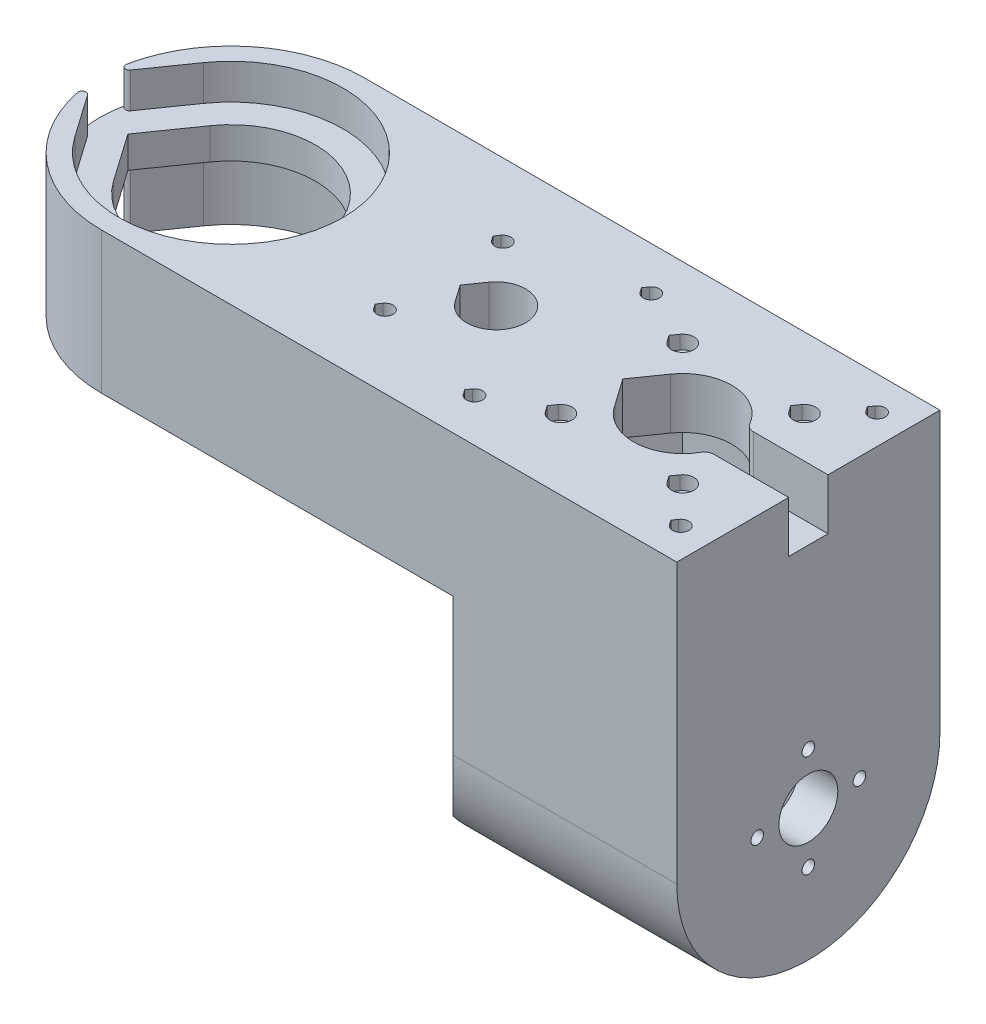
SolidWorks part; units mm, degrees
note: The reader was unsure of these and kept them because the rebuilt part matched: shared geometry of "Sketch2<4>", "Sketch2<5>", "Sketch2<6>", "Sketch3<3>", "Sketch4<3>", "Sketch6<8>", "Sketch6<9>", "Sketch6<10>", "Sketch6<13>", "Sketch6<14>", "Sketch11<3>", "Sketch16<2>".
ref_plane "Front Plane" through (0, 0, 0) normal (1, 0, 0) x (0, 1, 0)
ref_plane "Top Plane" through (0, 0, 0) normal (0, 0, 1) x (0, 1, 0)
ref_plane "Right Plane" through (0, 0, 0) normal (0, 1, 0) x (-1, 0, 0)
sketch "Sketch1" plane through (0, 0, 0) normal (0, 0, 1) x (0, 1, 0)
  line L0 (45, 28.55) -> (54, 28.55)
  line L1 (-7, -93) -> (58, -93)
  line L2 (-7, -93) -> (-7, -137)
  line L3 (-7, -137) -> (58, -137)
  line L4 (58, -93) -> (58, -137)
  line L5 (59, 28.55) -> (68, 28.55)
  line L6 (59, 28.55) -> (59, -28.55)
  line L7 (59, -28.55) -> (68, -28.55)
  line L8 (68, 28.55) -> (68, -28.55)
  line L9 (45, 28.55) -> (45, -28.55)
  line L10 (45, -28.55) -> (54, -28.55)
  line L11 (54, 28.55) -> (54, -28.55)
  line L12 (-13, -147) -> (13, -147)
  line L13 (-30, 30.9464) -> (30, 30.9464) construction
  line L14 (-30, 30.9464) -> (-30, -30.2553) construction
  line L15 (-30, -30.2553) -> (30, -30.2553) construction
  line L16 (30, 30.9464) -> (30, -30.2553) construction
  line L17 (-25, -83) -> (81, -83)
  line L20 (81, -83) -> (81, -147)
  line L21 (81, -83) -> (35, -83)
  line L23 (81, 33.5) -> (35, 33.5)
  line L25 (-25, -147) -> (-13, -147)
  line L26 (-25, -147) -> (-25, -150)
  line L27 (-25, -150) -> (25, -150)
  line L28 (25, -147) -> (25, -150)
  line L29 (13, -147) -> (25, -147)
  line L30 (25, -147) -> (81, -147)
  line L31 (81, -83) -> (81, 33.5)
  line L32 (35, 33.5) -> (35, -83)
  line L33 (-25, -147) -> (-33.5, -147)
  line L34 (-25, -83) -> (-33.5, -83)
  line L35 (-33.5, -83) -> (-33.5, -147)
  point P8 (0, -30.2553)
  point P14 (68, 0)
  point P15 (58, -115)
  point P24 (45, 0)
  point P35 (0, -147)
  dimension "D1" = 65
  dimension "D2" = 44
  dimension "D3" = 57.1
  dimension "D4" = 9
  dimension "D5" = 57.1
  dimension "D6" = 9
  dimension "D7" = 115
  dimension "D8" = 60
  dimension "D9" = 5
  dimension "D10" = 15
  dimension "D11" = 10
  dimension "D12" = 3
  dimension "D13" = 50
  dimension "D14" = 26
  dimension "D15" = 10
  dimension "D16" = 23
  dimension "D17" = 4.95
  dimension "D18" = 10
  dimension "D19" = 10
  dimension "D20" = 8.5
extrude "Boss-Extrude1" add sketch "Sketch1" along normal blind 67
sketch "Sketch2" plane through (0, 81, 0) normal (0, 1, 0) x (-1, 0, 0)
  line L0 (-56.7259, 33.5) -> (49943.2741, 33.5) construction
  line L1 (-147, 67) -> (-147, 0) construction
  line L2 (17.6118, 21.1681) -> (26.2467, 33.5)
  line L3 (-115, -14.8158) -> (-54, -14.8158) construction
  line L4 (-93, 0) -> (-137, 0) construction
  line L5 (-93, 0) -> (-137, 0) construction
  line L9 (-147, 16) -> (-147, 51)
  line L10 (33.5473, 15.9815) -> (-147, 51) construction
  line L11 (33.5482, 51) -> (-147, 16) construction
  line L12 (-54, 18.5) -> (-54, 48.5) construction
  line L13 (-104.0826, 51) -> (-125.9174, 51)
  line L14 (-130.5, 49) -> (-99.5, 49) construction
  line L15 (-130.5, 49) -> (-130.5, 18) construction
  line L16 (-130.5, 18) -> (-99.5, 18) construction
  line L17 (-99.5, 49) -> (-99.5, 18) construction
  line L18 (-130.5, 49) -> (-99.5, 18) construction
  line L19 (-130.5, 18) -> (-99.5, 49) construction
  line L20 (-135.0826, 51) -> (-147, 51)
  line L21 (-135.0826, 16) -> (-147, 16)
  line L22 (-104.0826, 16) -> (-125.9174, 16)
  line L27 (33.5, 67) -> (-21.8575, 67)
  line L28 (33.5, 0) -> (33.5, 67)
  line L29 (33.5, 67) -> (-147, 67) construction
  line L30 (33.5, 0) -> (-21.8575, 0)
  line L31 (28.55, 0) -> (-28.55, 0) construction
  line L34 (23.3868, 17.1244) -> (34.8531, 33.5)
  line L35 (34.8531, 33.5) -> (23.3868, 49.8756)
  line L36 (26.2467, 33.5) -> (17.6118, 45.8319)
  line L37 (-94.9174, 16) -> (-66.0711, 16)
  line L38 (-94.9174, 51) -> (-66.0711, 51)
  line L39 (-61.0711, 11) -> (-61.0711, 0)
  line L40 (33.5, 0) -> (-147, 0) construction
  line L41 (-61.0711, 56) -> (-61.0711, 67)
  line L42 (33.5, 67) -> (-147, 67) construction
  line L43 (-61.0711, 0) -> (-21.8575, 0)
  line L44 (-61.0711, 67) -> (-21.8575, 67)
  arc A0 (23.3868, 49.8756) -> (23.3868, 17.1244) centre (0, 33.5) ccw
  arc A2 (-39.8663, 36.7683) -> (-39.8653, 30.2204) centre (0, 33.5) ccw
  arc A5 (-135.0826, 16) -> (-125.9174, 16) centre (-130.5, 18) ccw
  arc A6 (-104.0826, 16) -> (-94.9174, 16) centre (-99.5, 18) ccw
  arc A9 (-125.9174, 51) -> (-135.0826, 51) centre (-130.5, 49) ccw
  arc A11 (-94.9174, 51) -> (-104.0826, 51) centre (-99.5, 49) ccw
  arc A12 (17.6118, 45.8319) -> (17.6118, 21.1681) centre (0, 33.5) ccw
  arc A13 (17.6118, 45.8319) -> (17.6118, 21.1681) centre (0, 33.5) cw construction
  arc A15 (23.3868, 17.1244) -> (23.3868, 49.8756) centre (0, 33.5) ccw construction
  arc A16 (-66.0711, 16) -> (-61.0711, 11) centre (-66.0711, 11) cw
  arc A17 (-66.0711, 51) -> (-61.0711, 56) centre (-66.0711, 56) ccw
  point P4 (-56.7259, 33.5)
  point P9 (-56.75, 33.4953)
  point P23 (-115, 33.5)
  point P39 (33.5, 33.5)
  point P61 (-54, 33.5)
  dimension "D1" = 57.1
  dimension "D2" = 35
  dimension "D3" = 80
  dimension "D6" = 5
  dimension "D9" = 10
  dimension "D10" = 43
  dimension "D11" = 55
  dimension "D12" = 10
  dimension "D4" = 61
  dimension "D5" = 30
  dimension "D8" = 31
  dimension "D13" = 55
extrude "Cut-Extrude1" cut sketch "Sketch2" against normal through all both and the other way through all contours A12 L2 L36
fillet "Fillet3" radius 34 2 edges at (-33.5, 58, 0) (-33.5, 58, 67)
extrude "Cut-Extrude2" cut sketch "Sketch2<4>" against normal blind 10 and the other way through all contours L20 L9 L21 A5 L22 A6 L37 A16 L39 L43 L30 L28 L27 L44 L41 A17 L38 A11 L13 A9
sketch "Sketch2<4>" plane through (0, 81, 0) normal (0, 1, 0) x (-1, 0, 0) same geometry as "Sketch2"
extrude "Cut-Extrude3" cut sketch "Sketch2<5>" against normal blind 9 from surface at -10 contours A0 L34 L35 starting at face at (81.1646, 71, 33.5)
sketch "Sketch2<5>" plane through (0, 81, 0) normal (0, 1, 0) x (-1, 0, 0) same geometry as "Sketch2"
extrude "Cut-Extrude4" cut sketch "Sketch2<6>" along normal blind 19 from surface at -46 contours A0 L34 L35 starting at face at (-7.4528, 35, 33.5)
sketch "Sketch2<6>" plane through (0, 81, 0) normal (0, 1, 0) x (-1, 0, 0) same geometry as "Sketch2"
sketch "Sketch3" plane through (0, 71, 0) normal (0, 1, 0) x (-1, 0, 0)
  line L0 (-93, 0) -> (-137, 0) construction
  line L1 (-93, 0) -> (-137, 0)
  line L2 (-115, 33.5) -> (-50115, 33.5) construction
  line L4 (-99.7403, 33.5) -> (-104.3338, 40.0179)
  line L5 (-127.65, 49) -> (-127, 49) construction
  line L6 (-130.5, 49) -> (-99.5, 49) construction
  line L7 (-130.5, 49) -> (-130.5, 18) construction
  line L8 (-130.5, 18) -> (-99.5, 18) construction
  line L9 (-99.5, 49) -> (-99.5, 18) construction
  line L12 (-128.9, 49) -> (-128.5, 49) construction
  line L13 (-129.22, 49.96) -> (-128.5, 49)
  line L14 (-129.22, 48.04) -> (-128.5, 49)
  line L15 (-128.1793, 50.6543) -> (-127, 49)
  line L16 (-127, 49) -> (-128.1793, 47.3457)
  line L17 (-96, 49) -> (-97.1793, 47.3457)
  line L18 (-97.1793, 50.6543) -> (-96, 49)
  line L19 (-98.22, 48.04) -> (-97.5, 49)
  line L20 (-98.22, 49.96) -> (-97.5, 49)
  line L21 (-96, 18) -> (-97.1793, 16.3457)
  line L22 (-97.1793, 19.6543) -> (-96, 18)
  line L23 (-98.22, 17.04) -> (-97.5, 18)
  line L24 (-98.22, 18.96) -> (-97.5, 18)
  line L25 (-127, 18) -> (-128.1793, 16.3457)
  line L26 (-128.1793, 19.6543) -> (-127, 18)
  line L27 (-129.22, 17.04) -> (-128.5, 18)
  line L28 (-129.22, 18.96) -> (-128.5, 18)
  line L29 (-115, 0) -> (-115, 33.5) construction
  line L30 (-147, 38.5) -> (-126.4564, 38.5)
  line L32 (-147, 28.5) -> (-126.4564, 28.5)
  line L34 (-167.5436, 38.5) -> (-126.4564, 28.5) construction
  line L35 (-167.5436, 28.5) -> (-126.4564, 38.5) construction
  line L36 (-147, 38.5) -> (-147, 28.5)
  line L38 (-104.7606, 26.3303) -> (-99.7403, 33.5)
  arc A0 (-128.1793, 50.6543) -> (-128.1793, 47.3457) centre (-130.5, 49) ccw
  arc A1 (-129.22, 49.96) -> (-129.22, 48.04) centre (-130.5, 49) ccw
  arc A2 (-129.22, 49.96) -> (-129.22, 48.04) centre (-130.5, 49) cw construction
  arc A3 (-128.1793, 50.6543) -> (-133.0893, 47.8092) centre (-130.5, 49) cw construction
  arc A4 (-97.1793, 50.6543) -> (-97.1793, 47.3457) centre (-99.5, 49) ccw
  arc A5 (-98.22, 49.96) -> (-98.22, 48.04) centre (-99.5, 49) ccw
  arc A6 (-98.22, 49.96) -> (-98.22, 48.04) centre (-99.5, 49) cw construction
  arc A7 (-97.1793, 50.6543) -> (-102.0893, 47.8092) centre (-99.5, 49) cw construction
  arc A8 (-97.1793, 19.6543) -> (-97.1793, 16.3457) centre (-99.5, 18) ccw
  arc A9 (-98.22, 18.96) -> (-98.22, 17.04) centre (-99.5, 18) ccw
  arc A10 (-98.22, 18.96) -> (-98.22, 17.04) centre (-99.5, 18) cw construction
  arc A11 (-97.1793, 19.6543) -> (-102.0893, 16.8092) centre (-99.5, 18) cw construction
  arc A12 (-128.1793, 19.6543) -> (-128.1793, 16.3457) centre (-130.5, 18) ccw
  arc A13 (-129.22, 18.96) -> (-129.22, 17.04) centre (-130.5, 18) ccw
  arc A14 (-129.22, 18.96) -> (-129.22, 17.04) centre (-130.5, 18) cw construction
  arc A15 (-128.1793, 19.6543) -> (-133.0893, 16.8092) centre (-130.5, 18) cw construction
  arc A18 (-126.4564, 28.5) -> (-104.7606, 26.3303) centre (-115, 33.5) ccw
  arc A19 (-104.3338, 40.0179) -> (-126.4564, 38.5) centre (-115, 33.5) ccw
  arc A20 (-104.3338, 40.0179) -> (-104.7606, 26.3303) centre (-115, 33.5) cw construction
  point P8 (-115, 33.5)
  point P24 (-147, 33.5)
  point P63 (-115, 49)
  dimension "D2" = 5.7
  dimension "D3" = 3.2
  dimension "D8" = 25
  dimension "D1" = 31
  dimension "D4" = 0.65
  dimension "D5" = 0.4
  dimension "D9" = 10
  dimension "D6" = 2
  dimension "D7" = 2
extrude "Cut-Extrude5" cut sketch "Sketch3" against normal up to vertex (13 mm away) contours L32 A18 L38 L4 A19 L30 L36 | A13 L27 L28 | A9 L23 L24 | A5 L19 L20 | A1 L14 L13 up to point (137, 58, 0)
extrude "Cut-Extrude6" cut sketch "Sketch3<3>" against normal blind 3.5 contours A0 L16 L15 | A12 L25 L26 | A4 L17 L18 | A8 L21 L22
sketch "Sketch3<3>" plane through (0, 71, 0) normal (0, 1, 0) x (-1, 0, 0) same geometry as "Sketch3"
sketch "Sketch4" plane through (0, 71, 0) normal (0, 1, 0) x (-1, 0, 0)
  line L0 (-115, 33.5) -> (-54.2, 33.5) construction
  line L1 (-54.2, 48.5) -> (-54.2, 18.5) construction
  line L2 (-52.8894, 49.4177) -> (-52.2468, 48.5)
  line L3 (-52.8894, 47.5823) -> (-52.2468, 48.5)
  line L4 (-52.2468, 48.5) -> (-52.6, 48.5) construction
  line L7 (-52.8894, 19.4177) -> (-52.2468, 18.5)
  line L8 (-51.95, 48.5) -> (-51.6974, 48.5) construction
  line L9 (-51.6974, 48.5) -> (-52.5207, 47.3242)
  line L10 (-52.5207, 49.6758) -> (-51.6974, 48.5)
  line L11 (-52.8894, 17.5823) -> (-52.2468, 18.5)
  line L12 (-52.2468, 18.5) -> (-52.6, 18.5) construction
  line L13 (-53.1972, 18.5) -> (-51.6974, 18.5) construction
  line L14 (-51.6974, 18.5) -> (-52.5207, 17.3242)
  line L15 (-52.5207, 19.6758) -> (-51.6974, 18.5)
  arc A1 (-52.8894, 49.4177) -> (-52.8894, 47.5823) centre (-54.2, 48.5) ccw
  arc A2 (-52.8894, 49.4177) -> (-52.8894, 47.5823) centre (-54.2, 48.5) cw construction
  arc A4 (-52.8894, 19.4177) -> (-52.8894, 17.5823) centre (-54.2, 18.5) ccw
  arc A5 (-52.5207, 49.6758) -> (-52.5207, 47.3242) centre (-54.2, 48.5) ccw
  arc A6 (-52.5207, 49.6758) -> (-52.5207, 47.3242) centre (-54.2, 48.5) cw construction
  arc A7 (-52.8894, 19.4177) -> (-52.8894, 17.5823) centre (-54.2, 18.5) cw construction
  arc A8 (-52.5207, 19.6758) -> (-52.5207, 17.3242) centre (-54.2, 18.5) ccw
  arc A9 (-52.5207, 19.6758) -> (-52.5207, 17.3242) centre (-54.2, 18.5) cw construction
  point P5 (-54.2, 33.5)
  dimension "D3" = 3.2
  dimension "D5" = 3.2
  dimension "D7" = 4.1
  dimension "D6" = 4.1
  dimension "D1" = 60.8
  dimension "D2" = 30
  dimension "D4" = 55
  dimension "D8" = 55
  dimension "D9" = 55
  dimension "D10" = 55
extrude "Cut-Extrude7" cut sketch "Sketch4" against normal blind 10 contours A1 L3 L2 | A4 L11 L7
extrude "Cut-Extrude8" cut sketch "Sketch4<3>" against normal blind 7
sketch "Sketch4<3>" plane through (0, 71, 0) normal (0, 1, 0) x (-1, 0, 0) same geometry as "Sketch4"
sketch "Sketch10" plane through (0, -33.5, 0) normal (0, -1, 0) x (1, 0, 0)
  line L0 (83, 67) -> (147, 0) construction
  line L1 (83, 0) -> (147, 67) construction
  line L2 (83, 0) -> (147, 0) construction
  line L3 (93, 55.5) -> (137, 55.5)
  line L4 (93, 11.5) -> (137, 11.5)
  line L5 (137, 55.5) -> (137, 11.5)
  line L6 (93, 55.5) -> (137, 11.5) construction
  line L7 (93, 11.5) -> (137, 55.5) construction
  line L8 (93, 55.5) -> (93, 43.5)
  line L9 (137, 33.5) -> (83, 33.5) construction
  line L10 (83, 43.5) -> (83, 23.5)
  line L11 (83, 23.5) -> (93, 23.5)
  line L12 (83, 43.5) -> (93, 43.5)
  line L13 (93, 23.5) -> (93, 11.5)
  point P9 (115, 33.5)
  point P10 (115, 33.5)
  point P20 (83, 33.5)
  dimension "D1" = 44
  dimension "D2" = 20
extrude "Cut-Extrude18" cut sketch "Sketch10" against normal up to surface (91.5 mm away) up to face at (122.4062, 58, 33.4581)
sketch "Sketch6" plane through (0, 35, 0) normal (0, -1, 0) x (1, 0, 0)
  line L0 (0, 33.5) -> (-26.2467, 33.5) construction
  line L1 (0, 33.5) -> (25.8751, 21.4342) construction
  line L2 (25.8751, 21.4342) -> (39.4317, 21.4342) construction
  line L3 (39.4317, 21.4342) -> (39.4317, 46.3342) construction
  line L4 (39.4317, 46.3342) -> (39.4317, 51.5342) construction
  line L5 (39.4317, 21.4342) -> (39.4317, 16.3342) construction
  line L6 (39.4317, 16.3342) -> (39.4317, 11.1342) construction
  line L9 (59.4317, 23.5) -> (59.4317, 43.5) construction
  line L13 (38.1211, 15.4165) -> (37.4785, 16.3342)
  line L14 (38.1211, 17.252) -> (37.4785, 16.3342)
  line L15 (37.4785, 16.3342) -> (37.8317, 16.3342) construction
  line L16 (37.3817, 16.3342) -> (36.9291, 16.3342) construction
  line L17 (36.9291, 16.3342) -> (37.7525, 17.5101)
  line L18 (37.7525, 15.1584) -> (36.9291, 16.3342)
  line L19 (38.1211, 45.4165) -> (37.4785, 46.3342)
  line L20 (38.1211, 47.252) -> (37.4785, 46.3342)
  line L21 (37.4785, 46.3342) -> (37.8317, 46.3342) construction
  line L22 (37.3817, 46.3342) -> (36.9291, 46.3342) construction
  line L23 (36.9291, 46.3342) -> (37.7525, 47.5101)
  line L24 (37.7525, 45.1584) -> (36.9291, 46.3342)
  line L25 (39.4317, 51.5342) -> (22.133, 51.5342)
  line L26 (39.4317, 11.1342) -> (17.7447, 11.1342)
  line L27 (39.4317, 11.1342) -> (59.4317, 11.1342)
  line L28 (39.4317, 51.5342) -> (59.4317, 51.5342)
  line L29 (59.4317, 51.5342) -> (59.4317, 43.5)
  line L30 (59.4317, 23.5) -> (83, 23.5)
  line L31 (59.4317, 23.5) -> (59.4317, 11.1342)
  line L32 (83, 67) -> (83, 43.5) construction
  line L33 (59.4317, 43.5) -> (83, 43.5)
  line L35 (83, 43.5) -> (83, 55.8658)
  line L36 (59.4317, 11.1342) -> (83, 11.1342)
  line L37 (83, 67) -> (83, 43.5) construction
  line L38 (83, 23.5) -> (83, 11.1342)
  line L40 (0.5, 0) -> (83, 0) construction
  line L41 (83, 55.8658) -> (59.4317, 55.8658)
  line L42 (59.4317, 51.5342) -> (59.4317, 55.8658)
  line L43 (0.5, 67) -> (83, 67) construction
  line L44 (75, 18.5) -> (75, 48.5)
  line L45 (83, 23.5) -> (83, 43.5)
  line L46 (73.6894, 49.4177) -> (73.0468, 48.5)
  line L47 (72.4974, 48.5) -> (73.3207, 49.6758)
  line L48 (67.5, 33.5) -> (58.3442, 33.5) construction
  line L49 (73.3207, 47.3242) -> (72.4974, 48.5)
  line L50 (73.6894, 47.5823) -> (73.0468, 48.5)
  line L51 (58.3442, 33.5) -> (61.3564, 29.1982)
  line L52 (58.3442, 33.5) -> (61.3564, 37.8018)
  line L54 (73.6894, 17.5823) -> (73.0468, 18.5)
  line L55 (73.3207, 17.3242) -> (72.4974, 18.5)
  line L56 (73.6894, 19.4177) -> (73.0468, 18.5)
  line L57 (72.4974, 18.5) -> (73.3207, 19.6758)
  line L58 (75, 48.5) -> (72.4974, 48.5) construction
  line L59 (75, 18.5) -> (72.4974, 18.5) construction
  arc A0 (-23.3868, 17.1244) -> (-23.3868, 49.8756) centre (0, 33.5) ccw construction
  arc A5 (38.1211, 15.4165) -> (38.1211, 17.252) centre (39.4317, 16.3342) ccw
  arc A6 (38.1211, 15.4165) -> (38.1211, 17.252) centre (39.4317, 16.3342) cw construction
  arc A7 (37.7525, 15.1584) -> (37.7525, 17.5101) centre (39.4317, 16.3342) ccw
  arc A8 (37.7525, 15.1584) -> (37.7525, 17.5101) centre (39.4317, 16.3342) cw construction
  arc A9 (38.1211, 45.4165) -> (38.1211, 47.252) centre (39.4317, 46.3342) ccw
  arc A10 (38.1211, 45.4165) -> (38.1211, 47.252) centre (39.4317, 46.3342) cw construction
  arc A11 (37.7525, 45.1584) -> (37.7525, 47.5101) centre (39.4317, 46.3342) ccw
  arc A12 (37.7525, 45.1584) -> (37.7525, 47.5101) centre (39.4317, 46.3342) cw construction
  arc A13 (-23.3868, 17.1244) -> (-23.3868, 49.8756) centre (0, 33.5) ccw construction
  arc A14 (22.133, 51.5342) -> (17.7447, 11.1342) centre (0, 33.5) cw
  arc A19 (73.6894, 47.5823) -> (73.6894, 49.4177) centre (75, 48.5) cw construction
  arc A20 (73.3207, 47.3242) -> (73.3207, 49.6758) centre (75, 48.5) ccw
  arc A21 (73.6894, 47.5823) -> (73.6894, 49.4177) centre (75, 48.5) ccw
  arc A22 (73.3207, 47.3242) -> (73.3207, 49.6758) centre (75, 48.5) cw construction
  arc A23 (73.3207, 17.3242) -> (73.3207, 19.6758) centre (75, 18.5) ccw
  arc A24 (73.3207, 17.3242) -> (73.3207, 19.6758) centre (75, 18.5) cw construction
  arc A25 (73.6894, 17.5823) -> (73.6894, 19.4177) centre (75, 18.5) ccw
  arc A26 (73.6894, 17.5823) -> (73.6894, 19.4177) centre (75, 18.5) cw construction
  arc A27 (61.3564, 29.1982) -> (61.3564, 37.8018) centre (67.5, 33.5) ccw
  arc A28 (60, 33.5) -> (61.3564, 29.1982) centre (67.5, 33.5) ccw construction
  arc A29 (61.3564, 37.8018) -> (60, 33.5) centre (67.5, 33.5) ccw construction
  point P9 (59.4317, 33.5)
  point P58 (75, 33.5)
  point P84 (73.4, 48.5)
  arc M9 (-23.3868, 49.8756) -> (-23.3868, 17.1244) centre (0, 33.5) cw
  line M91 (83, 23.5) -> (83, 43.5)
  dimension "D11" = 3.2
  dimension "D12" = 4.1
  dimension "D15" = 3.2
  dimension "D16" = 4.1
  dimension "D20" = 3.2
  dimension "D21" = 4.1
  dimension "D25" = 3.2
  dimension "D28" = 2.05
  dimension "D29" = 15
  dimension "D1" = 155
  dimension "D2" = 24.9
  dimension "D3" = 13.5566
  dimension "D4" = 5.2
  dimension "D5" = 5.2
  dimension "D6" = 5.1
  dimension "D13" = 55
  dimension "D14" = 55
  dimension "D17" = 55
  dimension "D18" = 55
  dimension "D19" = 20
  dimension "D7" = 20
  dimension "D8" = 11.1342
  dimension "D9" = 11.1342
  dimension "D10" = 30
  dimension "D24" = 8
  dimension "D22" = 125
  dimension "D23" = 55
  dimension "D26" = 125
  dimension "D27" = 55
  dimension "D30" = 55
extrude "Cut-Extrude24" cut sketch "Sketch6" against normal blind 10 contours L30 L44 L33 L29 L28 L25 L26 L27 L31 A11 L24 L23 A7 L18 L17 M9 | L44 L30 L33 M91 | L13 A5 L14 | L18 A7 L17 A5 L13 L14 | L24 A11 L23 A9 L19 L20 | L19 A9 L20
extrude "Cut-Extrude25" cut sketch "Sketch6<8>" against normal blind 5
sketch "Sketch6<8>" plane through (0, 35, 0) normal (0, -1, 0) x (1, 0, 0) same geometry as "Sketch6"
extrude "Cut-Extrude26" cut sketch "Sketch6<9>" against normal blind 20
sketch "Sketch6<9>" plane through (0, 35, 0) normal (0, -1, 0) x (1, 0, 0) same geometry as "Sketch6"
extrude "Cut-Extrude27" cut sketch "Sketch6<10>" against normal blind 7 from surface at -10 contours A7 L17 L18 | A11 L23 L24 starting at face at (56.5061, 45, 32.3025)
sketch "Sketch6<10>" plane through (0, 35, 0) normal (0, -1, 0) x (1, 0, 0) same geometry as "Sketch6"
extrude "Cut-Extrude28" cut sketch "Sketch6<13>" against normal blind 7 from surface at -5 contours A20 L47 L49 | A23 L57 L55 starting at face at (71.2159, 40, 17.3171)
sketch "Sketch6<13>" plane through (0, 35, 0) normal (0, -1, 0) x (1, 0, 0) same geometry as "Sketch6"
extrude "Cut-Extrude29" cut sketch "Sketch6<14>" against normal through all contours A27 L52 L51
sketch "Sketch6<14>" plane through (0, 35, 0) normal (0, -1, 0) x (1, 0, 0) same geometry as "Sketch6"
fillet "Fillet1" radius 5 2 edges at (61.0711, 76, 0) (61.0711, 76, 67)
fillet "Fillet2" radius 2.5 10 edges at (135.0826, 76, 16) (125.9174, 76, 16) (104.0826, 76, 16) (104.0826, 76, 51) (125.9174, 76, 51) (135.0826, 76, 51) (126.4564, 64.5, 28.5) (126.4564, 64.5, 38.5) (94.9174, 76, 51) (94.9174, 76, 16)
fillet "Fillet4" radius 1 4 edges at (-33.4026, 44.5, 31.4285) (-33.4026, 44.5, 35.5715) (-33.4026, 66.5, 35.5715) (-33.4026, 66.5, 31.4285)
chamfer "Chamfer7" distance 12 angle 45 2 edges at (93, 12.25, 43.5) (93, 12.25, 23.5)
sketch "Sketch11" plane through (137, 0, 0) normal (-1, 0, 0) x (0, -1, 0)
  line L0 (-71, 33.5) -> (-50071, 33.5) construction
  circle A0 centre (0, 33.5) radius 13 construction
  circle A1 centre (0, 33.5) radius 25
  circle A2 centre (0, 46.5) radius 1.6
  circle A3 centre (0, 46.5) radius 2.85
  circle A4 centre (13, 33.5) radius 2.85
  circle A5 centre (13, 33.5) radius 1.6
  circle A6 centre (0, 20.5) radius 2.85
  circle A7 centre (0, 20.5) radius 1.6
  circle A8 centre (-13, 33.5) radius 2.85
  circle A9 centre (-13, 33.5) radius 1.6
  dimension "D1" = 50
  dimension "D2" = 26
  dimension "D3" = 3.2
  dimension "D4" = 5.7
extrude "Cut-Extrude19" cut sketch "Sketch11" against normal through all contours A9 | A2 | A5 | A7
extrude "Cut-Extrude20" cut sketch "Sketch11<3>" against normal blind 3.5 contours A8 | A3 | A4 | A6
sketch "Sketch11<3>" plane through (137, 0, 0) normal (-1, 0, 0) x (0, -1, 0) same geometry as "Sketch11"
chamfer "Chamfer6" distance 7 angle 45 2 edges at (83, 0.75, 0) (83, 0.75, 67)
sketch "Sketch9" plane through (147, 0, 0) normal (1, 0, 0) x (0, 1, 0)
  line L0 (71, 33.5) -> (-49929, 33.5) construction
  line L2 (0, 67) -> (-54.5324, 67)
  line L4 (-54.5324, 67) -> (-54.5324, 0)
  line L5 (-54.5324, 0) -> (0, 0)
  arc A3 (0, 67) -> (0, 0) centre (0, 33.5) ccw
extrude "Cut-Extrude16" cut sketch "Sketch9" against normal up to surface (64 mm away) up to face at (83, 13.8333, 53.7886)
chamfer "Chamfer8" distance 5 angle 45 2 edges at (83, 4.3615, 45.5) (83, 4.3615, 21.5)
sketch "Sketch12" plane through (83, 0, 0) normal (-1, 0, 0) x (0, -1, 0)
  line L0 (25.2636, 55.5) -> (25.2636, 11.5)
  arc A0 (25.2636, 11.5) -> (25.2636, 55.5) centre (0, 33.5) ccw construction
  arc A1 (25.2636, 11.5) -> (25.2636, 55.5) centre (0, 33.5) ccw
extrude "Cut-Extrude21" cut sketch "Sketch12" against normal up to vertex (10 mm away) up to point (93, -25.2636, 11.5)
sketch "Sketch13" plane through (83, 0, 0) normal (-1, 0, 0) x (0, -1, 0)
  circle A0 centre (0, 46.5) radius 5
  circle A1 centre (0, 20.5) radius 5
  dimension "D1" = 10
  dimension "D2" = 10
extrude "Cut-Extrude22" cut sketch "Sketch13" against normal blind 10
fillet "Fillet6" radius 5 4 edges at (84.7678, -4.3094, 17.9645) (84.7678, 4.3094, 17.9645) (84.7678, 4.3094, 49.0355) (84.7678, -4.3094, 49.0355)
sketch "Sketch14" plane through (0, 81, 0) normal (0, 1, 0) x (-1, 0, 0)
  line L0 (-66.0711, 16) -> (-93.5, 16) construction
  line L1 (-105.5, 16) -> (-124.5, 16) construction
  line L2 (-136.5, 16) -> (-147, 16) construction
  line L3 (-147, 16) -> (-147, 0) construction
  line L4 (-147, 0) -> (-66.0711, 0) construction
  line L5 (-61.0711, 5) -> (-61.0711, 11) construction
  line L6 (-93.5, 51) -> (-66.0711, 51) construction
  line L7 (-61.0711, 56) -> (-61.0711, 62) construction
  line L8 (-66.0711, 67) -> (-147, 67) construction
  line L9 (-147, 67) -> (-147, 51) construction
  line L10 (-147, 51) -> (-136.5, 51) construction
  line L11 (-124.5, 51) -> (-105.5, 51) construction
  line L12 (-66.0711, 16) -> (-93.5, 16)
  line L13 (-105.5, 16) -> (-124.5, 16)
  line L14 (-136.5, 16) -> (-147, 16)
  line L15 (-147, 16) -> (-147, 0)
  line L16 (-147, 0) -> (-66.0711, 0)
  line L17 (-61.0711, 5) -> (-61.0711, 11)
  line L18 (-93.5, 51) -> (-66.0711, 51)
  line L19 (-61.0711, 56) -> (-61.0711, 62)
  line L20 (-66.0711, 67) -> (-147, 67)
  line L21 (-147, 67) -> (-147, 51)
  line L22 (-147, 51) -> (-136.5, 51)
  line L23 (-124.5, 51) -> (-105.5, 51)
  arc A0 (-93.5, 16) -> (-95.5, 15) centre (-93.5, 13.5) ccw construction
  arc A1 (-103.5, 15) -> (-95.5, 15) centre (-99.5, 18) ccw construction
  arc A2 (-103.5, 15) -> (-105.5, 16) centre (-105.5, 13.5) ccw construction
  arc A3 (-124.5, 16) -> (-126.5, 15) centre (-124.5, 13.5) ccw construction
  arc A4 (-134.5, 15) -> (-126.5, 15) centre (-130.5, 18) ccw construction
  arc A5 (-134.5, 15) -> (-136.5, 16) centre (-136.5, 13.5) ccw construction
  arc A6 (-66.0711, 0) -> (-61.0711, 5) centre (-66.0711, 5) ccw construction
  arc A7 (-61.0711, 11) -> (-66.0711, 16) centre (-66.0711, 11) ccw construction
  arc A8 (-95.5, 52) -> (-103.5, 52) centre (-99.5, 49) ccw construction
  arc A9 (-95.5, 52) -> (-93.5, 51) centre (-93.5, 53.5) ccw construction
  arc A10 (-66.0711, 51) -> (-61.0711, 56) centre (-66.0711, 56) ccw construction
  arc A11 (-61.0711, 62) -> (-66.0711, 67) centre (-66.0711, 62) ccw construction
  arc A12 (-136.5, 51) -> (-134.5, 52) centre (-136.5, 53.5) ccw construction
  arc A13 (-126.5, 52) -> (-134.5, 52) centre (-130.5, 49) ccw construction
  arc A14 (-126.5, 52) -> (-124.5, 51) centre (-124.5, 53.5) ccw construction
  arc A15 (-105.5, 51) -> (-103.5, 52) centre (-105.5, 53.5) ccw construction
  arc A16 (-93.5, 16) -> (-95.5, 15) centre (-93.5, 13.5) ccw
  arc A17 (-103.5, 15) -> (-95.5, 15) centre (-99.5, 18) ccw
  arc A18 (-103.5, 15) -> (-105.5, 16) centre (-105.5, 13.5) ccw
  arc A19 (-124.5, 16) -> (-126.5, 15) centre (-124.5, 13.5) ccw
  arc A20 (-134.5, 15) -> (-126.5, 15) centre (-130.5, 18) ccw
  arc A21 (-134.5, 15) -> (-136.5, 16) centre (-136.5, 13.5) ccw
  arc A22 (-66.0711, 0) -> (-61.0711, 5) centre (-66.0711, 5) ccw
  arc A23 (-61.0711, 11) -> (-66.0711, 16) centre (-66.0711, 11) ccw
  arc A24 (-95.5, 52) -> (-103.5, 52) centre (-99.5, 49) ccw
  arc A25 (-95.5, 52) -> (-93.5, 51) centre (-93.5, 53.5) ccw
  arc A26 (-66.0711, 51) -> (-61.0711, 56) centre (-66.0711, 56) ccw
  arc A27 (-61.0711, 62) -> (-66.0711, 67) centre (-66.0711, 62) ccw
  arc A28 (-136.5, 51) -> (-134.5, 52) centre (-136.5, 53.5) ccw
  arc A29 (-126.5, 52) -> (-134.5, 52) centre (-130.5, 49) ccw
  arc A30 (-126.5, 52) -> (-124.5, 51) centre (-124.5, 53.5) ccw
  arc A31 (-105.5, 51) -> (-103.5, 52) centre (-105.5, 53.5) ccw
extrude "Cut-Extrude23" cut sketch "Sketch14" against normal blind 10
sketch "Sketch16" plane through (0, 71, 0) normal (0, 1, 0) x (-1, 0, 0)
  line L0 (-84.5, 11) -> (-81.9974, 11) construction
  line L1 (-81.9974, 11) -> (-82.8207, 9.8242)
  line L2 (-81.9974, 11) -> (-82.8207, 12.1758)
  line L3 (-83.1894, 10.0823) -> (-82.5468, 11)
  line L4 (-83.1894, 11.9177) -> (-82.5468, 11)
  line L5 (-139.5, 8.5) -> (-136.9974, 8.5) construction
  line L6 (-136.9974, 8.5) -> (-137.8207, 7.3242)
  line L7 (-136.9974, 8.5) -> (-137.8207, 9.6758)
  line L8 (-138.1894, 7.5823) -> (-137.5468, 8.5)
  line L9 (-138.1894, 9.4177) -> (-137.5468, 8.5)
  line L10 (-139.5, 58.5) -> (-139.5, 8.5) construction
  line L15 (-139.5, 58.5) -> (-136.9974, 58.5) construction
  line L16 (-136.9974, 58.5) -> (-137.8207, 57.3242)
  line L17 (-136.9974, 58.5) -> (-137.8207, 59.6758)
  line L18 (-138.1894, 57.5823) -> (-137.5468, 58.5)
  line L19 (-138.1894, 59.4177) -> (-137.5468, 58.5)
  line L20 (-84.5, 56) -> (-81.9974, 56) construction
  line L21 (-81.9974, 56) -> (-82.8207, 54.8242)
  line L22 (-81.9974, 56) -> (-82.8207, 57.1758)
  line L23 (-83.1894, 55.0823) -> (-82.5468, 56)
  line L24 (-83.1894, 56.9177) -> (-82.5468, 56)
  line L25 (-84.5, 11) -> (-84.5, 56) construction
  arc A0 (-83.1894, 11.9177) -> (-83.1894, 10.0823) centre (-84.5, 11) ccw
  arc A3 (-82.8207, 12.1758) -> (-82.8207, 9.8242) centre (-84.5, 11) ccw
  arc A4 (-82.9, 11) -> (-83.1894, 11.9177) centre (-84.5, 11) ccw construction
  arc A5 (-83.1894, 10.0823) -> (-82.9, 11) centre (-84.5, 11) ccw construction
  arc A6 (-82.45, 11) -> (-82.8207, 12.1758) centre (-84.5, 11) ccw construction
  arc A7 (-82.8207, 9.8242) -> (-82.45, 11) centre (-84.5, 11) ccw construction
  arc A8 (-138.1894, 9.4177) -> (-138.1894, 7.5823) centre (-139.5, 8.5) ccw
  arc A9 (-137.8207, 9.6758) -> (-137.8207, 7.3242) centre (-139.5, 8.5) ccw
  arc A10 (-137.9, 8.5) -> (-138.1894, 9.4177) centre (-139.5, 8.5) ccw construction
  arc A11 (-138.1894, 7.5823) -> (-137.9, 8.5) centre (-139.5, 8.5) ccw construction
  arc A12 (-137.45, 8.5) -> (-137.8207, 9.6758) centre (-139.5, 8.5) ccw construction
  arc A13 (-137.8207, 7.3242) -> (-137.45, 8.5) centre (-139.5, 8.5) ccw construction
  arc A20 (-138.1894, 59.4177) -> (-138.1894, 57.5823) centre (-139.5, 58.5) ccw
  arc A21 (-137.8207, 59.6758) -> (-137.8207, 57.3242) centre (-139.5, 58.5) ccw
  arc A22 (-137.9, 58.5) -> (-138.1894, 59.4177) centre (-139.5, 58.5) ccw construction
  arc A23 (-138.1894, 57.5823) -> (-137.9, 58.5) centre (-139.5, 58.5) ccw construction
  arc A24 (-137.45, 58.5) -> (-137.8207, 59.6758) centre (-139.5, 58.5) ccw construction
  arc A25 (-137.8207, 57.3242) -> (-137.45, 58.5) centre (-139.5, 58.5) ccw construction
  arc A26 (-83.1894, 56.9177) -> (-83.1894, 55.0823) centre (-84.5, 56) ccw
  arc A27 (-82.8207, 57.1758) -> (-82.8207, 54.8242) centre (-84.5, 56) ccw
  arc A28 (-82.9, 56) -> (-83.1894, 56.9177) centre (-84.5, 56) ccw construction
  arc A29 (-83.1894, 55.0823) -> (-82.9, 56) centre (-84.5, 56) ccw construction
  arc A30 (-82.45, 56) -> (-82.8207, 57.1758) centre (-84.5, 56) ccw construction
  arc A31 (-82.8207, 54.8242) -> (-82.45, 56) centre (-84.5, 56) ccw construction
  point P1 (0, 33.5)
  point P19 (-84.5, 33.5)
  point P20 (-99.5, 49)
  point P21 (-139.5, 33.5)
  dimension "D1" = 3.2
  dimension "D2" = 4.1
  dimension "D3" = 3.2
  dimension "D4" = 4.1
  dimension "D9" = 15
  dimension "D10" = 45
  dimension "D13" = 3.2
  dimension "D14" = 4.1
  dimension "D17" = 3.2
  dimension "D18" = 4.1
  dimension "D5" = 55
  dimension "D6" = 55
  dimension "D7" = 55
  dimension "D8" = 55
  dimension "D11" = 40
  dimension "D12" = 50
  dimension "D15" = 55
  dimension "D16" = 55
  dimension "D19" = 55
  dimension "D20" = 55
extrude "Cut-Extrude30" cut sketch "Sketch16" against normal blind 7
extrude "Cut-Extrude31" cut sketch "Sketch16<2>" against normal blind 15 contours L19 A20 L18 | L9 A8 L8 | L4 A0 L3 | L24 A26 L23
sketch "Sketch16<2>" plane through (0, 71, 0) normal (0, 1, 0) x (-1, 0, 0) same geometry as "Sketch16"
chamfer "Chamfer11" distance 4.33 angle 45 1 edges at (59.4317, 37.5, 51.5342)
sketch "Sketch17" plane through (147, 0, 0) normal (1, 0, 0) x (0, 1, 0)
  circle A0 centre (0, 33.5) radius 13
  circle A1 centre (0, 33.5) radius 7.5
  point P3 (-13, 33.5)
  dimension "D1" = 15
extrude "Cut-Extrude32" cut sketch "Sketch17" against normal up to surface (10 mm away) contours A1 up to face at (137, 10.15, 33.5)
equation "\"D9@Sketch6\"=\"D8@Sketch6\""
